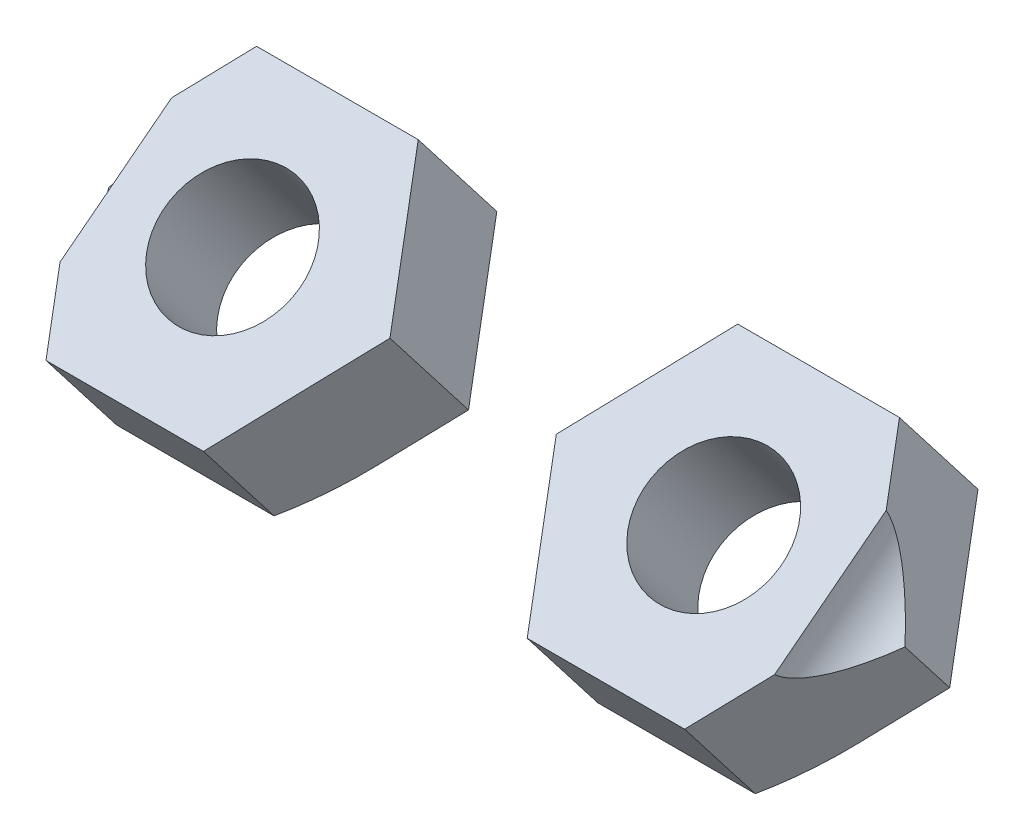
SolidWorks part; units mm, degrees
material "Plain Carbon Steel"
ref_plane "Front Plane" through (0, 0, 0) normal (0, 0, 1) x (1, 0, 0)
ref_plane "Top Plane" through (0, 0, 0) normal (0, 1, 0) x (1, 0, 0)
ref_plane "Right Plane" through (0, 0, 0) normal (1, 0, 0) x (0, 0, -1)
sketch "Sketch1" plane through (0, 0, 0) normal (0, 1, 0) x (1, 0, 0)
  line L0 (-35, 30) -> (35, 30)
  line L1 (-35, 30) -> (-35, -30)
  line L2 (35, 30) -> (35, -30)
  line L3 (-35, -30) -> (35, -30)
  line L4 (-35, 30) -> (35, -30) construction
  line L5 (35, 30) -> (-35, -30) construction
  point P1 (0, 0)
  dimension "D1" = 70
  dimension "D2" = 60
extrude "Boss-Extrude1" add sketch "Sketch1" along normal blind 23.5
sketch "Sketch2" plane through (35, 0, 0) normal (1, 0, 0) x (0, 0, -1)
  line L0 (-30, 23.5) -> (30, 23.5) construction
  line L1 (-30, 23.5) -> (-30, 0) construction
  line L2 (-30, 0) -> (30, 0) construction
  circle A0 centre (-18.25, 11.75) radius 4.5
  circle A1 centre (-18.25, 11.75) radius 11.75 construction
  dimension "D1" = 9
extrude "Cut-Extrude1" cut sketch "Sketch2" against normal through all
sketch "Sketch6" plane through (-35, 0, 0) normal (-1, 0, 0) x (0, 0, 1)
  line L0 (1.6334, 0) -> (-11.4458, 10.127)
  line L1 (-11.4458, 10.127) -> (5.0223, 31.3959)
  line L2 (5.0223, 31.3959) -> (-21.6002, 35.8847)
  line L3 (-21.6002, 35.8847) -> (-49.2641, 11.8212)
  line L4 (-49.2641, 11.8212) -> (1.6334, -46.6919)
  line L5 (1.6334, -46.6919) -> (1.6334, 0)
  line L7 (0, 0) -> (1.6334, 0) construction
  line L8 (-30, 0) -> (30, 0) construction
  dimension "D1" = 1
  dimension "D2" = 37.75
  dimension "D3" = 15.25
extrude "Cut-Extrude4" cut sketch "Sketch6" against normal through all
hole_wizard "M10 Tapped Hole1" positions "Sketch4" profile "Sketch3" tap size "M10" standard "ISO"
sketch "Sketch4" plane through (0, 11.8145, -13.6252) normal (0, -0.7907, -0.6122) x (-1, 0, 0)
  line L0 (-15, -11.0271) -> (15, -11.0271) construction
  line L5 (35, -11.0271) -> (15, -11.0271) construction
  line L8 (0, -19.2979) -> (0, -11.0271) construction
  line L9 (35, -19.2979) -> (35, -2.7563) construction
  line L10 (35, -19.2979) -> (-35, -19.2979) construction
  point P0 (-15, -11.0271)
  point P4 (15, -11.0271)
  dimension "D1" = 30
sketch "Sketch3" plane through (15, 5.0635, -4.9062) normal (1, 0, 0) x (0, 0.6122, -0.7907)
  line L0 (0, 0) -> (0, 30.0537)
  line L1 (0, 30.0537) -> (4.25, 27.5)
  line L2 (4.25, 27.5) -> (4.25, 0.775)
  line L3 (4.25, 0.775) -> (5.025, 0)
  line L5 (5.025, 0) -> (0, 0)
  line L6 (-4.25, 0.775) -> (-5.025, 0) construction
  line L10 (0, 30.0537) -> (-4.25, 27.5) construction
  line L11 (0, -6.35) -> (0, 107.95) construction
  dimension "Tap Drill Dia." = 8.5
  dimension "Tap Drill Depth" = 27.5
  dimension "Near C'Sink Dia." = 10.05
  dimension "Near C'Sink Angle" = 90
  dimension "Drill Angle" = 118
hole_wizard "M10 Tapped Hole2" positions "Sketch8" profile "Sketch7" tap size "M10" standard "ISO" end condition through all
sketch "Sketch8" plane through (0, 9.3363, -12.058) normal (0, 0.6122, -0.7907) x (-1, 0, 0)
  line L0 (-26.5, 9.4565) -> (26.5, 9.4565) construction
  line L2 (0, 9.4565) -> (0, 0) construction
  line L4 (-26.5, 1) -> (-26.5, 17.9131) construction
  line L5 (-35, 1) -> (35, 1) construction
  line L6 (35, 17.9131) -> (-35, 17.9131) construction
  point P0 (-26.5, 9.4565)
  point P2 (0, 9.4565)
  point P4 (26.5, 9.4565)
  dimension "D1" = 53
sketch "Sketch7" plane through (26.5, 16.8135, -6.2686) normal (1, 0, 0) x (0, 0.7907, 0.6122)
  line L0 (0, 0) -> (0, 38.9707)
  line L1 (0, 38.9707) -> (4.25, 38.9707)
  line L2 (4.25, 38.9707) -> (4.25, 0.775)
  line L3 (4.25, 0.775) -> (5.025, 0)
  line L5 (5.025, 0) -> (0, 0)
  line L6 (-4.25, 0.775) -> (-5.025, 0) construction
  line L11 (0, -6.35) -> (0, 107.95) construction
  dimension "Thread Major Dia." = 8.5
  dimension "Thru Tap Drill Depth" = 38.9707
  dimension "Near C'Sink Dia." = 10.05
  dimension "Near C'Sink Angle" = 90
sketch "Sketch5" plane through (0, 23.5, 0) normal (0, 1, 0) x (1, 0, 0)
  line L0 (-26.7593, -38.9566) -> (-26.7593, -7)
  line L1 (-26.7593, -38.9566) -> (-23.7593, -38.9566)
  line L2 (-26.7593, -7) -> (-23.7593, -7)
  line L3 (-23.7593, -38.9566) -> (-23.7593, -7)
  line L4 (-26.7593, -38.9566) -> (-23.7593, -7) construction
  line L5 (-26.7593, -7) -> (-23.7593, -38.9566) construction
  line L6 (-5.75, -34.8926) -> (-5.75, -7)
  line L7 (-5.75, -34.8926) -> (5.75, -34.8926)
  line L8 (-5.75, -7) -> (5.75, -7)
  line L9 (5.75, -34.8926) -> (5.75, -7)
  line L10 (-5.75, -34.8926) -> (5.75, -7) construction
  line L11 (-5.75, -7) -> (5.75, -34.8926) construction
  line L12 (0, 0) -> (0, -7) construction
  line L13 (26.7593, -38.9566) -> (23.7593, -38.9566)
  line L14 (26.7593, -38.9566) -> (26.7593, -7)
  line L15 (26.7593, -7) -> (23.7593, -7)
  line L16 (23.7593, -38.9566) -> (23.7593, -7)
  line L17 (-35, -30) -> (35, -30) construction
  point P1 (-25.2593, -22.9783)
  point P2 (0, -20.9463)
  dimension "D1" = 11.5
  dimension "D2" = 3
  dimension "D3" = 53.5185
  dimension "D4" = 23
extrude "Cut-Extrude2" cut sketch "Sketch5" against normal through all
chamfer "Chamfer1" distance 3 angle 45 8 edges at (-30.8796, 23.5, 30) (-14.7546, 23.5, 30) (14.7546, 23.5, 30) (30.8796, 23.5, 30) (30.8796, 0, 30) (14.7546, 0, 30) (-30.8796, 0, 30) (-14.7546, 0, 30)
fillet "Fillet1" radius 12 1 edges at (0, 0, 1.6334)
sketch "Sketch9" plane through (0, 10.7392, -12.2365) normal (0, 0.7907, 0.6122) x (-1, 0, 0)
  line L1 (19.9075, 0.7708) -> (24.815, 9.2708)
  line L2 (24.815, 9.2708) -> (19.9075, 17.7708)
  line L3 (19.9075, 17.7708) -> (10.0925, 17.7708)
  line L4 (10.0925, 17.7708) -> (5.185, 9.2708)
  line L5 (5.185, 9.2708) -> (10.0925, 0.7708)
  line L6 (10.0925, 0.7708) -> (19.9075, 0.7708)
  line L7 (-10.0925, 0.7708) -> (-5.185, 9.2708)
  line L8 (-5.185, 9.2708) -> (-10.0925, 17.7708)
  line L9 (-10.0925, 17.7708) -> (-19.9075, 17.7708)
  line L10 (-19.9075, 17.7708) -> (-24.815, 9.2708)
  line L11 (-24.815, 9.2708) -> (-19.9075, 0.7708)
  line L12 (-19.9075, 0.7708) -> (-10.0925, 0.7708)
  circle A0 centre (15, 9.2708) radius 8.5 construction
  circle A1 centre (-15, 9.2708) radius 8.5 construction
  dimension "D1" = 17
extrude "Cut-Extrude5" cut sketch "Sketch9" along normal blind 10 flip side to cut
sketch "Sketch10" plane through (35, 0, 0) normal (1, 0, 0) x (0, 0, -1)
  line L0 (-12.9006, 61.1186) -> (16.0106, 23.7792)
  line L1 (-12.9006, 61.1186) -> (-56.6721, 27.227)
  line L2 (16.0106, 23.7792) -> (-27.7609, -10.1123)
  line L3 (-56.6721, 27.227) -> (-27.7609, -10.1123)
  line L4 (-12.9006, 61.1186) -> (-27.7609, -10.1123) construction
  line L5 (16.0106, 23.7792) -> (-56.6721, 27.227) construction
  line L9 (4.9062, 5.0635) -> (11.4458, 10.127) construction
  point P1 (-20.3307, 25.5031)
  dimension "D1" = 8
extrude "Cut-Extrude6" cut sketch "Sketch10" against normal through all
